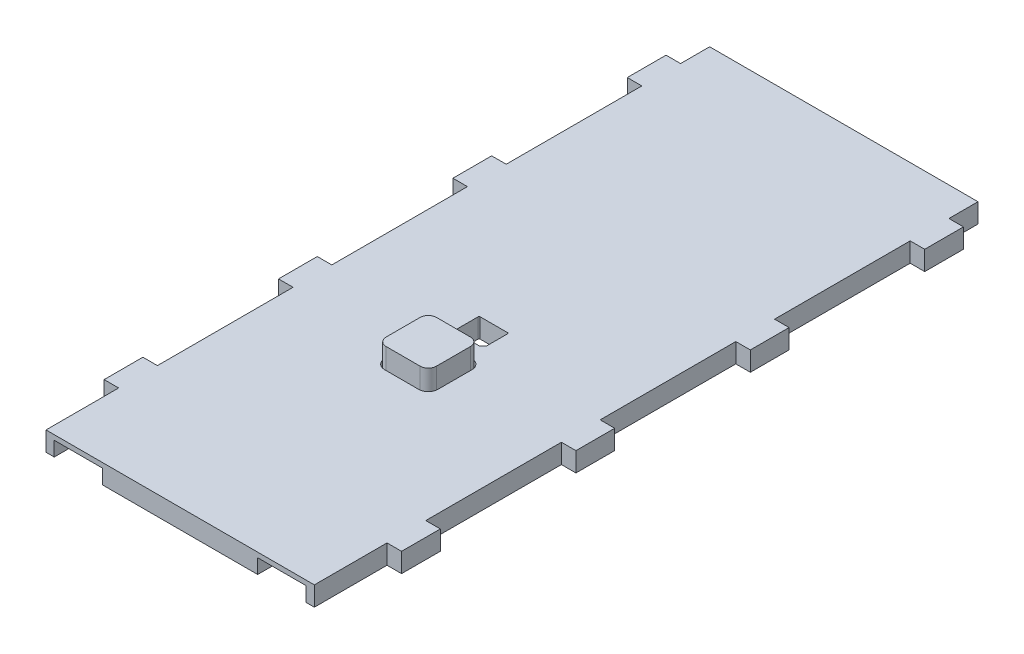
SolidWorks part; units mm, degrees
note: The reader was unsure of these and kept them because the rebuilt part matched: shared geometry of "草图6<3>".
material "PLA"
ref_plane "前视基准面" through (0, 0, 0) normal (0, 0, 1) x (1, 0, 0)
ref_plane "上视基准面" through (0, 0, 0) normal (0, 1, 0) x (1, 0, 0)
ref_plane "右视基准面" through (0, 0, 0) normal (1, 0, 0) x (0, 0, -1)
sketch "草图1" plane through (0, 0, 0) normal (0, 0, 1) x (1, 0, 0)
  line L21 (-13.85, 0) -> (13.85, 0)
  line L24 (13.85, 0) -> (13.85, 2)
  line L25 (13.85, 2) -> (-13.85, 2)
  line L26 (-13.85, 2) -> (-13.85, 0)
  point P0 (0, 0)
  dimension "D1" = 27.7
  dimension "D2" = 2
extrude "凸台-拉伸1" add sketch "草图1" along normal blind 70.5
ref_plane "基准面1" through (0, 0, 0) normal (1, 0, 0) x (0, 0, -1)
sketch "草图16" plane through (0, 0, 70.5) normal (0, 0, 1) x (1, 0, 0)
  line L0 (0, 0) -> (0, 2) construction
  line L1 (13.85, 2) -> (-13.85, 2) construction
  line L2 (-13.85, 0) -> (13.85, 0) construction
  line L3 (-13, 1.5) -> (-8, 1.5)
  line L4 (-13, 1.5) -> (-13, 0)
  line L5 (-13, 0) -> (-8, 0)
  line L6 (-8, 1.5) -> (-8, 0)
  line L7 (13, 0) -> (8, 0)
  line L8 (8, 1.5) -> (8, 0)
  line L9 (13, 1.5) -> (8, 1.5)
  line L10 (13, 1.5) -> (13, 0)
  dimension "D1" = 8
  dimension "D2" = 5
  dimension "D3" = 1.5
extrude "切除-拉伸6" cut sketch "草图16" against normal blind 5
sketch "草图4" plane through (0, 2, 0) normal (0, 1, 0) x (1, 0, 0)
  line L0 (1.8997, -42.991) -> (-1.9003, -46.791) construction
  line L2 (-2.7503, -42.141) -> (2.7497, -42.141)
  line L3 (-2.7503, -42.141) -> (-2.7503, -47.641)
  line L4 (-2.7503, -47.641) -> (2.7497, -47.641)
  line L5 (2.7497, -42.141) -> (2.7497, -47.641)
  line L6 (-2.7503, -42.141) -> (2.7497, -47.641) construction
  line L7 (-2.7503, -47.641) -> (2.7497, -42.141) construction
  line L8 (1.2997, -47.391) -> (2.4997, -46.191)
  line L9 (2.4997, -46.191) -> (2.4997, -43.591)
  line L10 (2.4997, -43.591) -> (1.2997, -42.391)
  line L11 (1.2997, -42.391) -> (-1.3003, -42.391)
  line L12 (-1.3003, -42.391) -> (-2.5003, -43.591)
  line L13 (-2.5003, -43.591) -> (-2.5003, -46.191)
  line L14 (-2.5003, -46.191) -> (-1.3003, -47.391)
  line L15 (-1.3003, -47.391) -> (1.2997, -47.391)
  line L16 (1.2997, -47.391) -> (2.4997, -46.191) construction
  line L17 (2.4997, -46.191) -> (2.4997, -43.591) construction
  line L18 (2.4997, -43.591) -> (1.2997, -42.391) construction
  line L19 (1.2997, -42.391) -> (-1.3003, -42.391) construction
  line L20 (-1.3003, -42.391) -> (-2.5003, -43.591) construction
  line L21 (-2.5003, -43.591) -> (-2.5003, -46.191) construction
  line L22 (-2.5003, -46.191) -> (-1.3003, -47.391) construction
  line L23 (-1.3003, -47.391) -> (1.2997, -47.391) construction
  point P6 (-0.0003, -44.891)
  dimension "D2" = 5.5
  dimension "D1" = 0
extrude "切除-拉伸2" cut sketch "草图4" against normal through all
fillet "圆角1" radius 1 4 edges at (-2.7503, 1, 47.641) (2.7497, 1, 47.641) (2.7497, 1, 42.141) (-2.7503, 1, 42.141)
sketch "草图5" plane through (0, 0, 0) normal (0, -1, 0) x (1, 0, 0)
  line L0 (-2.6003, 46.641) -> (-2.6003, 43.141)
  line L1 (-1.7503, 42.291) -> (1.7497, 42.291)
  line L2 (2.5997, 43.141) -> (2.5997, 46.641)
  line L3 (1.7497, 47.491) -> (-1.7503, 47.491)
  line L4 (-2.7503, 46.641) -> (-2.7503, 43.141)
  line L5 (1.7497, 47.641) -> (-1.7503, 47.641)
  line L6 (2.7497, 43.141) -> (2.7497, 46.641)
  line L7 (-1.7503, 42.141) -> (1.7497, 42.141)
  line L8 (-2.7503, 46.641) -> (-2.7503, 43.141) construction
  line L9 (1.7497, 47.641) -> (-1.7503, 47.641) construction
  line L10 (2.7497, 43.141) -> (2.7497, 46.641) construction
  line L11 (-1.7503, 42.141) -> (1.7497, 42.141) construction
  arc A0 (-2.6003, 43.141) -> (-1.7503, 42.291) centre (-1.7503, 43.141) ccw
  arc A1 (1.7497, 42.291) -> (2.5997, 43.141) centre (1.7497, 43.141) ccw
  arc A2 (2.5997, 46.641) -> (1.7497, 47.491) centre (1.7497, 46.641) ccw
  arc A3 (-1.7503, 47.491) -> (-2.6003, 46.641) centre (-1.7503, 46.641) ccw
  arc A4 (-1.7503, 47.641) -> (-2.7503, 46.641) centre (-1.7503, 46.641) ccw
  arc A5 (2.7497, 46.641) -> (1.7497, 47.641) centre (1.7497, 46.641) ccw
  arc A6 (1.7497, 42.141) -> (2.7497, 43.141) centre (1.7497, 43.141) ccw
  arc A7 (-2.7503, 43.141) -> (-1.7503, 42.141) centre (-1.7503, 43.141) ccw
  arc A8 (-1.7503, 47.641) -> (-2.7503, 46.641) centre (-1.7503, 46.641) ccw construction
  arc A9 (2.7497, 46.641) -> (1.7497, 47.641) centre (1.7497, 46.641) ccw construction
  arc A10 (1.7497, 42.141) -> (2.7497, 43.141) centre (1.7497, 43.141) ccw construction
  arc A11 (-2.7503, 43.141) -> (-1.7503, 42.141) centre (-1.7503, 43.141) ccw construction
  dimension "D1" = 0
  dimension "D2" = 0.15
extrude "凸台-拉伸3" add sketch "草图5" against normal blind 4 separate body
sketch "草图6" plane through (0, 0, 0) normal (0, -1, 0) x (1, 0, 0)
  line L0 (-2.0833, 47.423) -> (-4.788, 46.271)
  line L1 (-4.788, 43.5109) -> (-2.0833, 42.3589)
  line L2 (-4.2003, 44.891) -> (-2.6003, 44.891) construction
  line L3 (-0.0003, 42.291) -> (-0.0003, 47.491) construction
  line L5 (-2.6003, 46.641) -> (-2.6003, 43.141)
  line L6 (-1.7503, 42.291) -> (1.7497, 42.291)
  line L7 (2.5997, 43.141) -> (2.5997, 46.641)
  line L12 (1.7497, 47.491) -> (-1.7503, 47.491)
  line L13 (-2.6003, 46.641) -> (-2.6003, 43.141)
  line L14 (-1.7503, 42.291) -> (1.7497, 42.291)
  line L15 (2.5997, 43.141) -> (2.5997, 46.641)
  line L16 (1.7497, 47.491) -> (-1.7503, 47.491)
  line L17 (2.0828, 47.423) -> (4.7875, 46.271)
  line L18 (4.7875, 43.5109) -> (2.0828, 42.3589)
  arc A2 (-4.788, 46.271) -> (-4.788, 43.5109) centre (-4.2003, 44.891) ccw
  circle A12 centre (-4.2003, 44.891) radius 0.9
  circle A13 centre (4.1997, 44.891) radius 0.9
  arc A14 (4.7875, 46.271) -> (4.7875, 43.5109) centre (4.1997, 44.891) cw
  arc A15 (-1.7503, 47.491) -> (-2.6003, 46.641) centre (-1.7503, 46.641) ccw
  arc A16 (-2.6003, 43.141) -> (-1.7503, 42.291) centre (-1.7503, 43.141) ccw
  arc A17 (1.7497, 42.291) -> (2.5997, 43.141) centre (1.7497, 43.141) ccw
  arc A18 (2.5997, 46.641) -> (1.7497, 47.491) centre (1.7497, 46.641) ccw
  arc A19 (-1.7503, 47.491) -> (-2.6003, 46.641) centre (-1.7503, 46.641) ccw
  arc A20 (-2.6003, 43.141) -> (-1.7503, 42.291) centre (-1.7503, 43.141) ccw
  arc A21 (1.7497, 42.291) -> (2.5997, 43.141) centre (1.7497, 43.141) ccw
  arc A22 (2.5997, 46.641) -> (1.7497, 47.491) centre (1.7497, 46.641) ccw
  arc M15 (-1.7503, 47.491) -> (-2.6003, 46.641) centre (-1.7503, 46.641) ccw
  line M16 (-2.6003, 46.641) -> (-2.6003, 43.141)
  arc M17 (-2.6003, 43.141) -> (-1.7503, 42.291) centre (-1.7503, 43.141) ccw
  line M18 (-1.7503, 42.291) -> (1.7497, 42.291)
  arc M19 (1.7497, 42.291) -> (2.5997, 43.141) centre (1.7497, 43.141) ccw
  line M20 (2.5997, 43.141) -> (2.5997, 46.641)
  arc M21 (2.5997, 46.641) -> (1.7497, 47.491) centre (1.7497, 46.641) ccw
  line M22 (1.7497, 47.491) -> (-1.7503, 47.491)
  dimension "D2" = 3
  dimension "D3" = 1.8
  dimension "D4" = 1.6
  dimension "D1" = 0
extrude "凸台-拉伸4" add sketch "草图6" along normal blind 2 contours L0 A2 L1 A12 M17 M16 M15 | M22 M15 M16 M17 M18 M19 M20 M21 | A14 L17 L18 A13 M21 M20 M19
sketch "草图7" plane through (0, 0, 0) normal (0, -1, 0) x (1, 0, 0)
  circle A0 centre (4.1997, 44.891) radius 0.75
  circle A1 centre (-4.2003, 44.891) radius 0.75
  dimension "D1" = 1.5
extrude "凸台-拉伸5" add sketch "草图7" along normal offset from surface (4.5 mm away) 2.5 up to face at (-0.0003, -2, 44.891) offset beyond the face yes
extrude "凸台-拉伸6" add sketch "草图6<3>" along normal blind 3 from surface at 2 starting at face at (-0.0003, -2, 44.891)
sketch "草图6<3>" plane through (0, 0, 0) normal (0, -1, 0) x (1, 0, 0) same geometry as "草图6"
sketch "草图17" plane through (0, 2, 0) normal (0, 1, 0) x (1, 0, 0)
  line L0 (1.3813, -40.2814) -> (1.3813, -38.081) construction
  line L1 (1.3813, -40.2814) -> (1.0388, -40.6239) construction
  line L2 (-1.5616, -40.6239) -> (1.0388, -40.6239) construction
  line L3 (-1.6612, -38.081) -> (-1.6612, -40.5243) construction
  line L4 (13.85, 0) -> (-13.85, 0)
  line L5 (-13.85, 0) -> (-13.85, -70.5)
  line L6 (-13.85, -70.5) -> (13.85, -70.5)
  line L7 (13.85, -70.5) -> (13.85, 0)
  line L8 (13.85, 0) -> (-13.85, 0)
  line L9 (-13.85, 0) -> (-13.85, -70.5)
  line L10 (-13.85, -70.5) -> (13.85, -70.5)
  line L11 (13.85, -70.5) -> (13.85, 0)
  line L12 (1.2817, -37.9814) -> (-1.5616, -37.9814) construction
  line L13 (1.3813, -40.2814) -> (1.3813, -38.081)
  line L14 (1.3813, -40.2814) -> (1.0388, -40.6239)
  line L15 (-1.5616, -40.6239) -> (1.0388, -40.6239)
  line L16 (-1.6612, -38.081) -> (-1.6612, -40.5243)
  line L17 (1.2817, -37.9814) -> (-1.5616, -37.9814)
  ellipse E0 centre (-1.5608, -40.5235) end of major axis (-1.6321, -40.5948) minor radius 0.1 (-1.6612, -40.5243) -> (-1.5616, -40.6239) ccw construction
  ellipse E1 centre (-1.5608, -38.0818) end of major axis (-1.6321, -38.0105) minor radius 0.1 (-1.5616, -37.9814) -> (-1.6612, -38.081) ccw construction
  ellipse E2 centre (1.2809, -38.0818) end of major axis (1.3522, -38.0105) minor radius 0.1 (1.3813, -38.081) -> (1.2817, -37.9814) ccw construction
  ellipse E3 centre (-1.5608, -40.5235) end of major axis (-1.6321, -40.5948) minor radius 0.1 (-1.6612, -40.5243) -> (-1.5616, -40.6239) ccw
  ellipse E4 centre (-1.5608, -38.0818) end of major axis (-1.6321, -38.0105) minor radius 0.1 (-1.5616, -37.9814) -> (-1.6612, -38.081) ccw
  ellipse E5 centre (1.2809, -38.0818) end of major axis (1.3522, -38.0105) minor radius 0.1 (1.3813, -38.081) -> (1.2817, -37.9814) ccw
  dimension "D1" = 0
extrude "切除-拉伸7" cut sketch "草图17" against normal up to next (2 mm away) contours E3 L15 L14 L13 E5 L17 E4 L16
sketch "草图18" plane through (0, 2, 0) normal (0, 1, 0) x (1, 0, 0)
  line L0 (-13.85, -2) -> (13.85, -2) construction
  line L1 (-13.85, -2) -> (13.85, -2) construction
  line L2 (-13.85, 0) -> (-13.85, -2)
  line L3 (-13.85, -70.5) -> (-13.85, 0) construction
  line L4 (-13.85, -2) -> (13.85, -2)
  line L5 (13.85, -70.5) -> (13.85, 0) construction
  line L6 (13.85, -2) -> (13.85, 0)
  line L7 (13.85, 0) -> (-13.85, 0)
extrude "切除-拉伸8" cut sketch "草图18" against normal through all
sketch "草图19" plane through (-13.85, 0, 0) normal (-1, 0, 0) x (0, 0, 1)
  line L0 (41, 2) -> (45, 2) construction
  line L1 (45, 2) -> (45, 0) construction
  line L2 (45, 0) -> (41, 0) construction
  line L3 (41, 0) -> (41, 2) construction
  line L4 (9, 2) -> (5, 2)
  line L5 (9, 0) -> (9, 2)
  line L6 (5, 0) -> (9, 0)
  line L7 (5, 2) -> (5, 0)
  line L8 (9, 2) -> (5, 2)
  line L9 (9, 0) -> (9, 2)
  line L10 (5, 0) -> (9, 0)
  line L11 (5, 2) -> (5, 0)
  line L12 (23, 2) -> (27, 2) construction
  line L13 (27, 2) -> (27, 0) construction
  line L14 (27, 0) -> (23, 0) construction
  line L15 (23, 0) -> (23, 2) construction
  line L16 (41, 2) -> (45, 2)
  line L17 (45, 2) -> (45, 0)
  line L18 (45, 0) -> (41, 0)
  line L19 (41, 0) -> (41, 2)
  line L20 (23, 2) -> (27, 2)
  line L21 (27, 2) -> (27, 0)
  line L22 (27, 0) -> (23, 0)
  line L23 (23, 0) -> (23, 2)
  line L28 (63, 2) -> (59, 2)
  line L29 (63, 0) -> (63, 2)
  line L30 (59, 0) -> (63, 0)
  line L31 (59, 2) -> (59, 0)
  line L32 (63, 2) -> (59, 2)
  line L33 (63, 0) -> (63, 2)
  line L34 (59, 0) -> (63, 0)
  line L35 (59, 2) -> (59, 0)
  dimension "D1" = 0
  dimension "D2" = 0
extrude "凸台-拉伸7" add sketch "草图19" along normal blind 1.5
sketch "草图20" plane through (13.85, 0, 0) normal (1, 0, 0) x (0, 0, -1)
  line L0 (-5, 2) -> (-5, 0) construction
  line L1 (-5, 0) -> (-9, 0) construction
  line L2 (-9, 0) -> (-9, 2) construction
  line L3 (-9, 2) -> (-5, 2) construction
  line L4 (-23, 2) -> (-23, 0) construction
  line L5 (-23, 0) -> (-27, 0) construction
  line L6 (-27, 0) -> (-27, 2) construction
  line L7 (-27, 2) -> (-23, 2) construction
  line L8 (-41, 2) -> (-41, 0) construction
  line L9 (-41, 0) -> (-45, 0) construction
  line L10 (-45, 0) -> (-45, 2) construction
  line L11 (-45, 2) -> (-41, 2) construction
  line L12 (-59, 2) -> (-59, 0) construction
  line L13 (-59, 0) -> (-63, 0) construction
  line L14 (-63, 0) -> (-63, 2) construction
  line L15 (-63, 2) -> (-59, 2) construction
  line L16 (-70.5, 0) -> (-2, 0) construction
  line L17 (-2, 0) -> (-2, 2) construction
  line L18 (-2, 2) -> (-70.5, 2) construction
  line L19 (-70.5, 2) -> (-70.5, 0) construction
  line L20 (-5, 2) -> (-5, 0)
  line L21 (-5, 0) -> (-9, 0)
  line L22 (-9, 0) -> (-9, 2)
  line L23 (-9, 2) -> (-5, 2)
  line L24 (-23, 2) -> (-23, 0)
  line L25 (-23, 0) -> (-27, 0)
  line L26 (-27, 0) -> (-27, 2)
  line L27 (-27, 2) -> (-23, 2)
  line L28 (-41, 2) -> (-41, 0)
  line L29 (-41, 0) -> (-45, 0)
  line L30 (-45, 0) -> (-45, 2)
  line L31 (-45, 2) -> (-41, 2)
  line L32 (-59, 2) -> (-59, 0)
  line L33 (-59, 0) -> (-63, 0)
  line L34 (-63, 0) -> (-63, 2)
  line L35 (-63, 2) -> (-59, 2)
  line L36 (-70.5, 0) -> (-2, 0)
  line L37 (-2, 0) -> (-2, 2)
  line L38 (-2, 2) -> (-70.5, 2)
  line L39 (-70.5, 2) -> (-70.5, 0)
  line M17 (-70.5, 0) -> (-2, 0)
  line M19 (-2, 2) -> (-70.5, 2)
extrude "凸台-拉伸9" add sketch "草图20" along normal blind 1.5 contours L34 L32 M17 M19 | L31 L28 L29 L30 | L24 L25 L26 L27 | L23 L20 L21 L22
sketch "草图21" plane through (0, 0, 2) normal (0, 0, -1) x (-1, 0, 0)
  line L0 (-13, 0) -> (-13, 1.5) construction
  line L1 (-13, 1.5) -> (-8, 1.5) construction
  line L2 (-8, 1.5) -> (-8, 0) construction
  line L3 (-8, 0) -> (-13, 0) construction
  line L4 (13, 1.5) -> (13, 0) construction
  line L5 (13, 0) -> (8, 0) construction
  line L6 (8, 0) -> (8, 1.5) construction
  line L7 (8, 1.5) -> (13, 1.5) construction
  line L8 (-13, 0) -> (-13, 1.5)
  line L9 (-13, 1.5) -> (-8, 1.5)
  line L10 (-8, 1.5) -> (-8, 0)
  line L11 (-8, 0) -> (-13, 0)
  line L12 (13, 1.5) -> (13, 0)
  line L13 (13, 0) -> (8, 0)
  line L14 (8, 0) -> (8, 1.5)
  line L15 (8, 1.5) -> (13, 1.5)
extrude "切除-拉伸9" cut sketch "草图21" against normal blind 5
